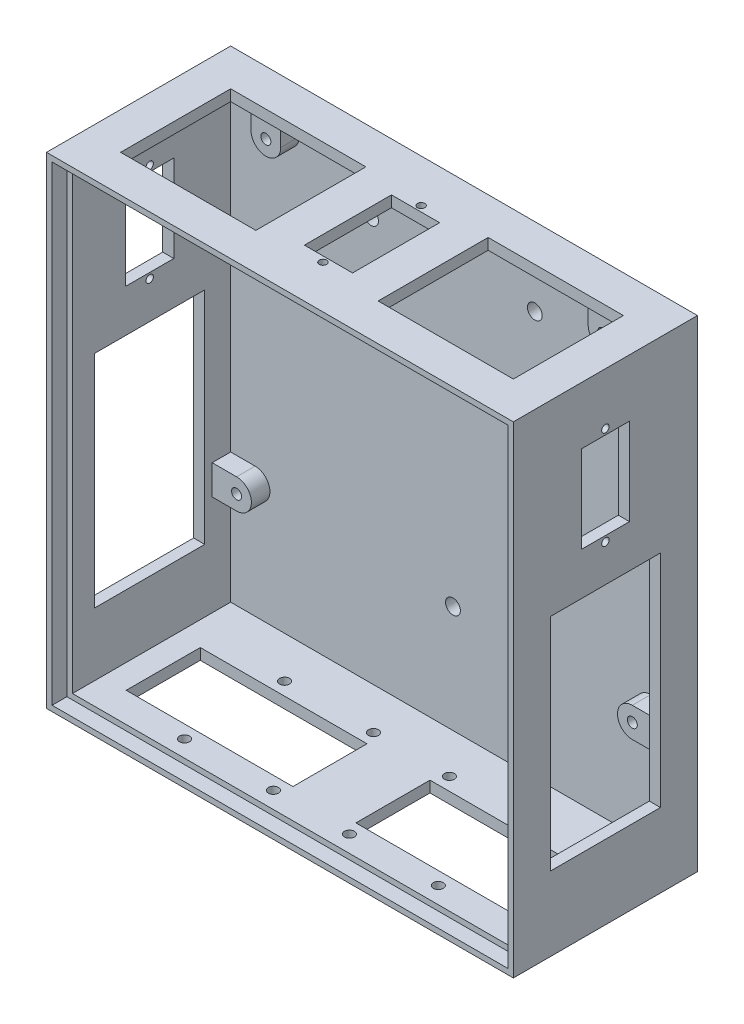
SolidWorks part; units mm, degrees
ref_plane "Front Plane" through (0, 0, 0) normal (0, 0, 1) x (1, 0, 0)
ref_plane "Top Plane" through (0, 0, 0) normal (0, 1, 0) x (1, 0, 0)
ref_plane "Right Plane" through (0, 0, 0) normal (1, 0, 0) x (0, 0, -1)
sketch "Sketch1" plane through (0, 0, 0) normal (0, 0, 1) x (1, 0, 0)
  line L1 (63, 65) -> (-63, 65)
  line L2 (63, 65) -> (63, -65)
  line L3 (63, -65) -> (-63, -65)
  line L4 (-63, 65) -> (-63, -65)
  line L5 (63, 65) -> (-63, -65) construction
  line L6 (63, -65) -> (-63, 65) construction
  point P0 (0, 0)
  dimension "D1" = 126
  dimension "D2" = 130
extrude "Boss-Extrude1" add sketch "Sketch1" along normal blind 49.7
sketch "Sketch2" plane through (0, 0, 49.7) normal (0, 0, 1) x (1, 0, 0)
  line L0 (-63, 65) -> (-63, -65) construction
  line L1 (60, 62) -> (-60, 62)
  line L2 (60, 62) -> (60, -62)
  line L3 (60, -62) -> (-60, -62)
  line L4 (-60, 62) -> (-60, -62)
  line L5 (60, 62) -> (-60, -62) construction
  line L6 (60, -62) -> (-60, 62) construction
  line L7 (63, 65) -> (-63, 65) construction
  line L9 (61.5, 63.5) -> (-61.5, 63.5)
  line L10 (61.5, 63.5) -> (61.5, -63.5)
  line L11 (61.5, -63.5) -> (-61.5, -63.5)
  line L12 (-61.5, 63.5) -> (-61.5, -63.5)
  line L13 (61.5, 63.5) -> (-61.5, -63.5) construction
  line L14 (61.5, -63.5) -> (-61.5, 63.5) construction
  point P0 (0, 0)
  point P10 (0, 0)
  dimension "D1" = 3
  dimension "D2" = 3
  dimension "D3" = 1.5
  dimension "D4" = 1.5
extrude "Cut-Extrude1" cut sketch "Sketch2" against normal offset from surface (46.7 mm away) 3 contours L1 L4 L3 L2 region at (0, 0, 49.7) up to face at (0, 0, 0)
extrude "Cut-Extrude2" cut sketch "Sketch2<3>" against normal blind 4
sketch "Sketch2<3>" plane through (0, 0, 49.7) normal (0, 0, 1) x (1, 0, 0) same geometry as "Sketch2"
sketch "Sketch3" plane through (0, 0, 3) normal (0, 0, 1) x (1, 0, 0)
  line L0 (41.5, 56) -> (41.5, 62)
  line L1 (60, 62) -> (-60, 62) construction
  line L2 (49.5, 56) -> (49.5, 62)
  line L3 (60, 62) -> (-60, 62) construction
  line L4 (0, -55) -> (0, 55) construction
  arc A0 (41.5, 56) -> (49.5, 56) centre (45.5, 56) ccw
  circle A2 centre (45.5, 56) radius 1.35
  line M3 (60, 62) -> (-60, 62)
  dimension "D2" = 4
  dimension "D3" = 2.7
  dimension "D1" = 6
  dimension "D4" = 45.5
extrude "Boss-Extrude2" add sketch "Sketch3" along normal blind 5 contours L0 A0 L2 A2 M3 region at (45.5, 57.5033, 3)
mirror "Mirror1" about plane through (0, 0, 0) normal (1, 0, 0) of "Boss-Extrude2"
sketch "Sketch4" plane through (0, 0, 3) normal (0, 0, 1) x (1, 0, 0)
  line L0 (53.4, -26.9) -> (60, -26.9)
  line L1 (60, 62) -> (60, -62) construction
  line L2 (53.4, -34.9) -> (60, -34.9)
  arc A0 (53.4, -26.9) -> (53.4, -34.9) centre (53.4, -30.9) ccw
  circle A1 centre (53.4, -30.9) radius 1.35
  circle A2 centre (45.5, 56) radius 1.35 construction
  line M9 (60, -62) -> (60, 62)
  dimension "D2" = 4
  dimension "D3" = 2.7
  dimension "D4" = 86.9
  dimension "D1" = 6.6
extrude "Boss-Extrude3" add sketch "Sketch4" along normal blind 5 contours L0 A0 L2 A1 M9 region at (55.2222, -30.9, 3)
mirror "Mirror2" about plane through (0, 0, 0) normal (1, 0, 0) of "Boss-Extrude3"
sketch "Sketch5" plane through (0, 65, 0) normal (0, 1, 0) x (1, 0, 0)
  line L0 (0, -24.85) -> (6.5, -24.85) construction
  line L1 (6.5, -13.1) -> (-6.5, -13.1)
  line L2 (6.5, -13.1) -> (6.5, -36.6)
  line L3 (6.5, -36.6) -> (-6.5, -36.6)
  line L4 (-6.5, -13.1) -> (-6.5, -36.6)
  line L5 (6.5, -13.1) -> (-6.5, -36.6) construction
  line L6 (6.5, -36.6) -> (-6.5, -13.1) construction
  line L7 (63, -49.7) -> (63, 0) construction
  circle A0 centre (0, -11.6) radius 1
  circle A1 centre (0, -38.1) radius 1
  point P0 (0, -24.85)
  point P8 (0, -13.1)
  point P12 (63, -24.85)
  dimension "D3" = 2
  dimension "D1" = 13
  dimension "D2" = 23.5
  dimension "D4" = 1.5
extrude "Cut-Extrude5" cut sketch "Sketch5" against normal up to surface (3 mm away) up to face at (0, 62, 11.7833)
sketch "Sketch7" plane through (63, 0, 0) normal (1, 0, 0) x (0, 0, -1)
  line L0 (-49.7, 65) -> (0, 65) construction
  line L1 (-18.35, 49.5) -> (-31.35, 49.5)
  line L2 (-18.35, 49.5) -> (-18.35, 26)
  line L3 (-18.35, 26) -> (-31.35, 26)
  line L4 (-31.35, 49.5) -> (-31.35, 26)
  line L5 (-18.35, 49.5) -> (-31.35, 26) construction
  line L6 (-18.35, 26) -> (-31.35, 49.5) construction
  line L8 (-24.85, 37.75) -> (-18.35, 37.75) construction
  circle A0 centre (-24.85, 51) radius 1
  circle A1 centre (-24.85, 24.5) radius 1
  point P0 (-24.85, 37.75)
  point P7 (-24.85, 65)
  dimension "D4" = 2
  dimension "D1" = 23.5
  dimension "D2" = 27.25
  dimension "D3" = 13
  dimension "D5" = 1.5
extrude "Cut-Extrude6" cut sketch "Sketch7" against normal up to surface (3 mm away) up to face at (60, -15.45, 14.925)
mirror "Mirror4" about plane through (0, 0, 0) normal (1, 0, 0) of "Cut-Extrude6"
sketch "Sketch8" plane through (0, -65, 0) normal (0, -1, 0) x (1, 0, 0)
  line L1 (-8.5, 37.7) -> (-53.5, 37.7)
  line L2 (-8.5, 37.7) -> (-8.5, 17.7)
  line L3 (-8.5, 17.7) -> (-53.5, 17.7)
  line L4 (-53.5, 37.7) -> (-53.5, 17.7)
  line L5 (-63, 0) -> (63, 0) construction
  circle A2 centre (-10.25, 41.2) radius 1.35
  circle A3 centre (-34.25, 41.2) radius 1.35
  circle A4 centre (-34.25, 14.2) radius 1.35
  circle A5 centre (-10.25, 14.2) radius 1.35
  dimension "D4" = 2.7
  dimension "D1" = 8.5
  dimension "D2" = 45
  dimension "D3" = 20
  dimension "D5" = 1.75
  dimension "D6" = 24
  dimension "D7" = 3.5
  dimension "D8" = 3.5
  dimension "D9" = 17.7
extrude "Cut-Extrude7" cut sketch "Sketch8" against normal up to surface (3 mm away) up to face at (0, -62, 24.35)
mirror "Mirror5" about plane through (0, 0, 0) normal (1, 0, 0) of "Cut-Extrude7"
sketch "Sketch9" plane through (0, 0, 0) normal (0, 0, -1) x (-1, 0, 0)
  line L0 (-63, 65) -> (63, 65) construction
  circle A0 centre (-22.1, 47) radius 2
  circle A1 centre (0, -33.01) radius 2
  dimension "D1" = 4
  dimension "D4" = 80.01
  dimension "D2" = 18
  dimension "D3" = 22.1
extrude "Cut-Extrude8" cut sketch "Sketch9" against normal up to surface (3 mm away) up to face at (0, 10.84, 3)
mirror "Mirror6" about plane through (0, 0, 0) normal (1, 0, 0) of "Cut-Extrude8"
sketch "Sketch10" plane through (63, 0, 0) normal (1, 0, 0) x (0, 0, -1)
  line L0 (-49.7, -65) -> (0, -65) construction
  line L1 (-39.7, 14.5) -> (-10, 14.5)
  line L2 (-39.7, 14.5) -> (-39.7, -45)
  line L3 (-39.7, -45) -> (-10, -45)
  line L4 (-10, 14.5) -> (-10, -45)
  line L5 (-49.7, -65) -> (-49.7, 65) construction
  line L7 (0, -65) -> (0, 65) construction
  circle A0 centre (-24.85, 24.5) radius 1 construction
  dimension "D3" = 10
  dimension "D1" = 20
  dimension "D2" = 10
  dimension "D4" = 10
extrude "Cut-Extrude9" cut sketch "Sketch10" against normal up to surface (126 mm away) up to face at (-63, 0, 24.85)
sketch "Sketch11" plane through (0, 65, 0) normal (0, 1, 0) x (1, 0, 0)
  line L0 (63, -49.7) -> (63, 0) construction
  line L1 (16.5, -10) -> (53, -10)
  line L2 (16.5, -10) -> (16.5, -39.7)
  line L3 (16.5, -39.7) -> (53, -39.7)
  line L4 (53, -10) -> (53, -39.7)
  line L5 (63, -49.7) -> (-63, -49.7) construction
  line L6 (6.5, -36.6) -> (6.5, -13.1) construction
  line L8 (63, 0) -> (-63, 0) construction
  dimension "D1" = 10
  dimension "D2" = 10
  dimension "D3" = 10
  dimension "D4" = 10
extrude "Cut-Extrude10" cut sketch "Sketch11" against normal up to surface (3 mm away) up to face at (0, 62, 39.1)
mirror "Mirror7" about plane through (0, 0, 0) normal (1, 0, 0) of "Cut-Extrude10"
